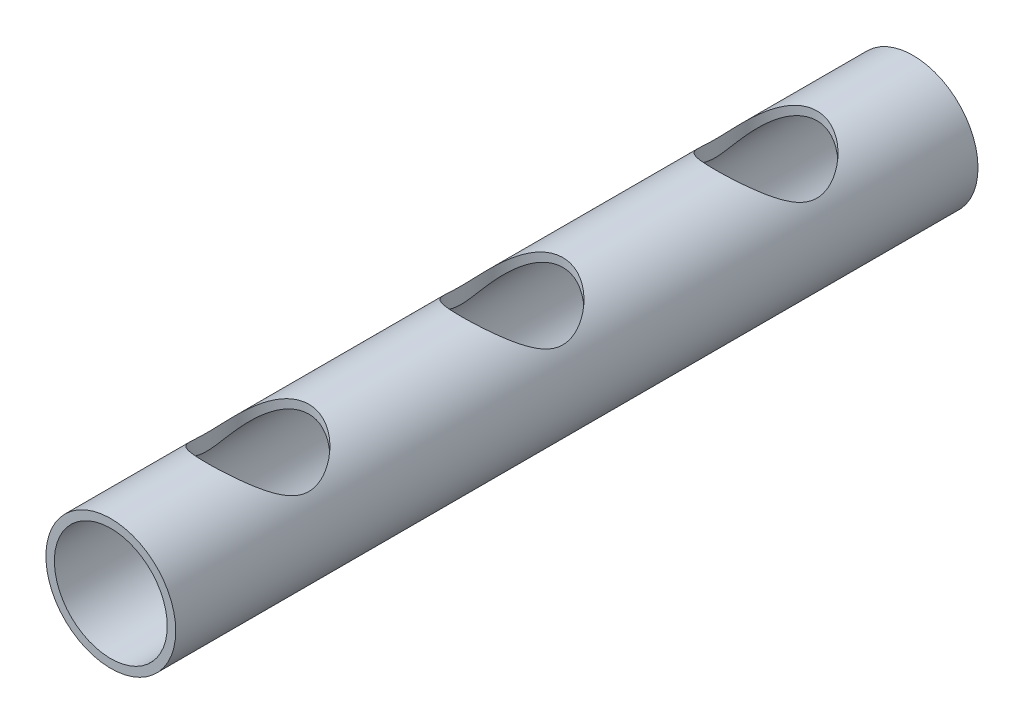
SolidWorks part; units mm, degrees
material "ABS"
ref_plane "Front Plane" through (0, 0, 0) normal (0, 0, 1) x (1, 0, 0)
ref_plane "Top Plane" through (0, 0, 0) normal (0, 1, 0) x (1, 0, 0)
ref_plane "Right Plane" through (0, 0, 0) normal (1, 0, 0) x (0, 0, -1)
sketch "Sketch1" plane through (0, 0, 0) normal (0, 0, 1) x (1, 0, 0)
  circle A0 centre (0, 0) radius 24.28
  circle A1 centre (0, 0) radius 21.105
  dimension "D1" = 48.56
  dimension "D2" = 3.175
extrude "Boss-Extrude1" add sketch "Sketch1" along normal blind 300
sketch "Sketch2" plane through (0, 0, 0) normal (0, 1, 0) x (1, 0, 0)
  line L0 (-24.28, -300) -> (24.28, -300) construction
  line L1 (24.28, 0) -> (-24.28, 0) construction
  circle A0 centre (0, -245) radius 19.05
  circle A1 centre (0, -150) radius 19.05
  circle A2 centre (0, -55) radius 19.05
  dimension "D1" = 38.1
  dimension "D3" = 55
  dimension "D4" = 55
  dimension "D2" = 3
extrude "Cut-Extrude1" cut sketch "Sketch2" along normal blind 100
